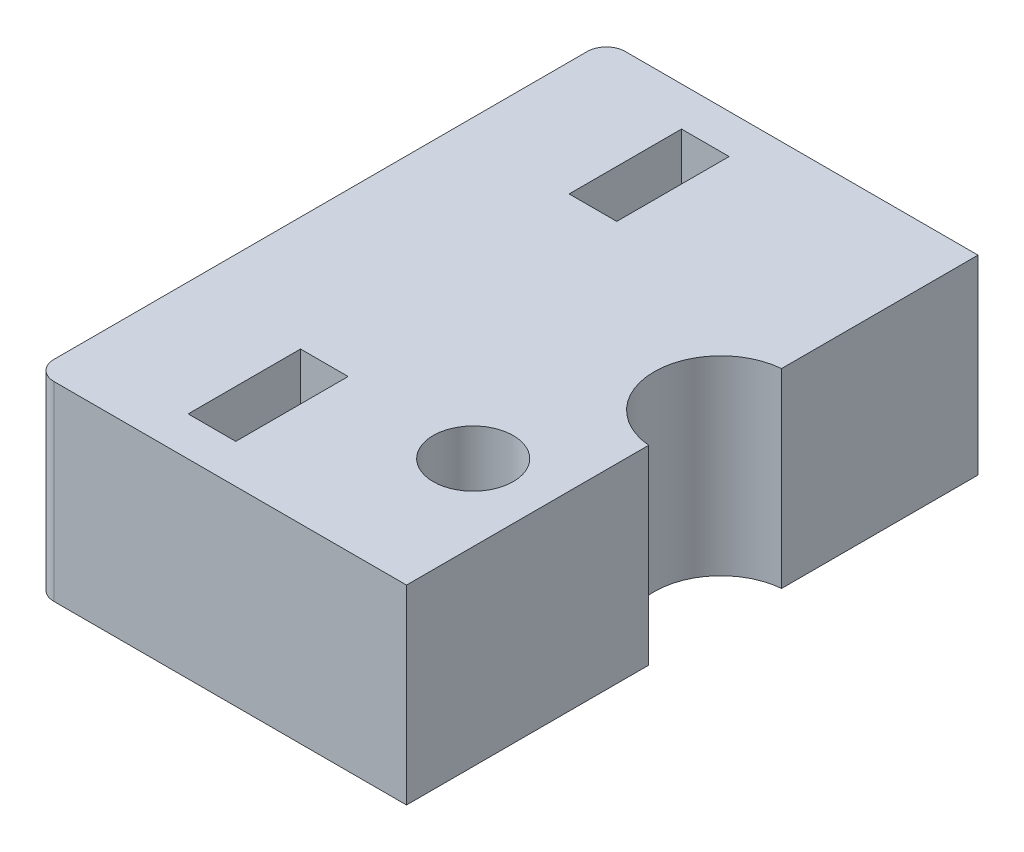
SolidWorks part; units mm, degrees
ref_plane "Front Plane" through (0, 0, 0) normal (0, 0, 1) x (1, 0, 0)
ref_plane "Top Plane" through (0, 0, 0) normal (0, 1, 0) x (1, 0, 0)
ref_plane "Right Plane" through (0, 0, 0) normal (1, 0, 0) x (0, 0, -1)
sketch "Sketch1" plane through (0, 0, 0) normal (0, 1, 0) x (1, 0, 0)
  line L1 (-29.5136, -15) -> (29.5136, -15)
  line L2 (-29.5136, -15) -> (-29.5136, 15)
  line L3 (-29.5136, 15) -> (29.5136, 15)
  line L4 (29.5136, -15) -> (29.5136, 15)
  line L5 (-29.5136, -15) -> (29.5136, 15) construction
  line L6 (-29.5136, 15) -> (29.5136, -15) construction
  point P0 (0, 0)
  dimension "D1" = 59.0272
  dimension "D2" = 30
extrude "Boss-Extrude1" add sketch "Sketch1" along normal blind 10
sketch "Sketch2" plane through (0, 10, 0) normal (0, 1, 0) x (1, 0, 0)
  line L0 (-14, -7.5) -> (6, -7.5) construction
  line L1 (-29.5136, 15) -> (-29.5136, -15) construction
  line L3 (-4, 15) -> (-4, -15) construction
  line L5 (-29.5136, -15) -> (29.5136, -15) construction
  circle A0 centre (-14, -7.5) radius 2.1
  circle A1 centre (6, -7.5) radius 2.1
  point P3 (-4, -7.5)
  dimension "D1" = 4.2
  dimension "D2" = 20
  dimension "D3" = 7.5
  dimension "D4" = 25.5136
extrude "Cut-Extrude1" cut sketch "Sketch2" against normal through all
sketch "Sketch3" plane through (29.5136, 0, 0) normal (1, 0, 0) x (0, 0, -1)
  line L0 (0, 10) -> (0, 0) construction
  line L1 (-15, 10) -> (15, 10) construction
  line L2 (-15, 0) -> (15, 0) construction
  line L3 (-10, 5) -> (10, 5) construction
  circle A0 centre (-10, 5) radius 1.65
  circle A1 centre (10, 5) radius 1.65
  point P9 (0, 5)
  dimension "D2" = 3.3
  dimension "D1" = 20
extrude "Cut-Extrude2" cut sketch "Sketch3" against normal blind 12
sketch "Sketch4" plane through (-29.5136, 0, 0) normal (-1, 0, 0) x (0, 0, 1)
  line L0 (0, 10) -> (0, 0) construction
  line L3 (-10, 5) -> (10, 5) construction
  line L4 (-15, 10) -> (15, 10) construction
  circle A0 centre (-10, 5) radius 1.7
  circle A1 centre (10, 5) radius 1.7
  point P9 (0, 5)
  dimension "D2" = 3.4
  dimension "D1" = 20
extrude "Cut-Extrude3" cut sketch "Sketch4" against normal blind 12
ref_plane "Plane1" through (23.5136, 0, 0) normal (1, 0, 0) x (0, 0, -1)
ref_plane "Plane2" through (-23.5136, 0, 0) normal (-1, 0, 0) x (0, 0, 1)
sketch "Sketch5" plane through (23.5136, 0, 0) normal (1, 0, 0) x (0, 0, -1)
  line L0 (-12.85, 6.6454) -> (-12.85, 10)
  line L1 (-7.15, 6.6454) -> (-10, 8.2909) construction
  line L2 (-10, 8.2909) -> (-12.85, 6.6454) construction
  line L3 (-12.85, 6.6454) -> (-12.85, 3.3546)
  line L4 (-12.85, 3.3546) -> (-10, 1.7091)
  line L5 (-10, 1.7091) -> (-7.15, 3.3546)
  line L6 (-7.15, 3.3546) -> (-7.15, 6.6454)
  line L7 (10, 8.2909) -> (7.15, 6.6454) construction
  line L8 (7.15, 6.6454) -> (7.15, 3.3546)
  line L9 (7.15, 3.3546) -> (10, 1.7091)
  line L10 (10, 1.7091) -> (12.85, 3.3546)
  line L11 (12.85, 3.3546) -> (12.85, 6.6454)
  line L12 (12.85, 6.6454) -> (10, 8.2909) construction
  line L13 (-15, 10) -> (15, 10) construction
  line L14 (-12.85, 10) -> (-7.15, 10)
  line L15 (-7.15, 10) -> (-7.15, 6.6454)
  line L16 (7.15, 6.6454) -> (7.15, 10)
  line L17 (7.15, 10) -> (12.85, 10)
  line L18 (12.85, 10) -> (12.85, 6.6454)
  circle A0 centre (-10, 5) radius 2.85 construction
  circle A1 centre (10, 5) radius 2.85 construction
  dimension "D1" = 5.7
extrude "Cut-Extrude4" cut sketch "Sketch5" against normal blind 2.3
sketch "Sketch6" plane through (-23.5136, 0, 0) normal (-1, 0, 0) x (0, 0, 1)
  line L0 (-12.95, 6.7032) -> (-12.95, 10)
  line L1 (-7.05, 6.7032) -> (-10, 8.4064) construction
  line L2 (-10, 8.4064) -> (-12.95, 6.7032) construction
  line L3 (-12.95, 6.7032) -> (-12.95, 3.2968)
  line L4 (-12.95, 3.2968) -> (-10, 1.5936)
  line L5 (-10, 1.5936) -> (-7.05, 3.2968)
  line L6 (-7.05, 3.2968) -> (-7.05, 6.7032)
  line L7 (10, 8.4064) -> (7.05, 6.7032) construction
  line L8 (7.05, 6.7032) -> (7.05, 3.2968)
  line L9 (7.05, 3.2968) -> (10, 1.5936)
  line L10 (10, 1.5936) -> (12.95, 3.2968)
  line L11 (12.95, 3.2968) -> (12.95, 6.7032)
  line L12 (12.95, 6.7032) -> (10, 8.4064) construction
  line L14 (-12.95, 10) -> (-7.05, 10)
  line L15 (-7.05, 10) -> (-7.05, 6.7032)
  line L16 (7.05, 6.7032) -> (7.05, 10)
  line L17 (7.05, 10) -> (12.95, 10)
  line L18 (12.95, 10) -> (12.95, 6.7032)
  line L19 (-15, 10) -> (15, 10) construction
  circle A0 centre (-10, 5) radius 2.95 construction
  circle A1 centre (10, 5) radius 2.95 construction
  circle A2 centre (-10, 5) radius 1.7 construction
  circle A3 centre (-10, 5) radius 1.7 construction
  circle A5 centre (10, 5) radius 1.7 construction
  circle A6 centre (10, 5) radius 1.7 construction
  dimension "D1" = 5.9
extrude "Cut-Extrude5" cut sketch "Sketch6" against normal blind 2.5
sketch "Sketch7" plane through (0, 10, 0) normal (0, 1, 0) x (1, 0, 0)
  line L0 (29.5136, -15) -> (29.5136, 15) construction
  line L1 (-29.5136, -15) -> (29.5136, -15) construction
  line L2 (15.7, 1.2) -> (-9.7, 1.2) construction
  circle A0 centre (15.7, 1.2) radius 3.5
  circle A1 centre (-9.7, 1.2) radius 3.5
  dimension "D3" = 7
  dimension "D1" = 13.8136
  dimension "D2" = 16.2
  dimension "D4" = 25.4
extrude "Cut-Extrude6" cut sketch "Sketch7" against normal through all
fillet "Fillet1" radius 1 4 edges at (-29.5136, 5, 15) (-29.5136, 5, -15) (29.5136, 5, -15) (29.5136, 5, 15)
sketch "Sketch8" plane through (0, 10, 0) normal (0, 1, 0) x (1, 0, 0)
  line L0 (-10, 15) -> (-10, -15)
  line L1 (28.5136, 15) -> (-28.5136, 15) construction
  line L2 (-28.5136, -15) -> (28.5136, -15) construction
  line L3 (-10, -15) -> (29.5136, -15)
  line L4 (29.5136, -15) -> (29.5136, 15)
  line L5 (29.5136, 15) -> (-10, 15)
  line L6 (29.5136, -14) -> (29.5136, 14) construction
  dimension "D1" = 10
extrude "Cut-Extrude7" cut sketch "Sketch8" against normal through all
